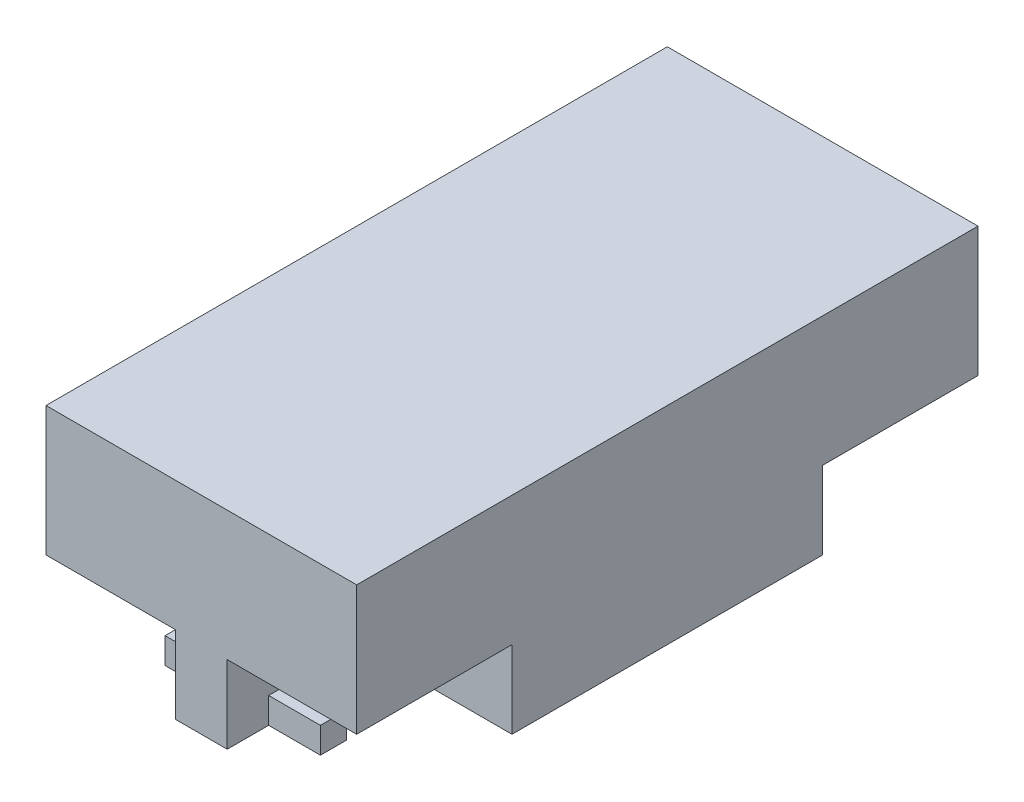
SolidWorks part; units mm, degrees
ref_plane "Front Plane" through (0, 0, 0) normal (0, 0, 1) x (1, 0, 0)
ref_plane "Top Plane" through (0, 0, 0) normal (0, 1, 0) x (1, 0, 0)
ref_plane "Right Plane" through (0, 0, 0) normal (1, 0, 0) x (0, 0, -1)
sketch "Sketch2" plane through (0, 0, 0) normal (1, 0, 0) x (0, 0, -1)
  line L1 (-300, 100) -> (300, 100)
  line L2 (-300, 100) -> (-300, -100)
  line L3 (-300, -100) -> (300, -100)
  line L4 (300, 100) -> (300, -100)
  line L5 (-300, 100) -> (300, -100) construction
  line L6 (-300, -100) -> (300, 100) construction
  point P0 (0, 0)
  dimension "D1" = 600
  dimension "D2" = 200
extrude "Boss-Extrude1" add sketch "Sketch2" along normal blind 150 and the other way blind 150
sketch "Sketch3" plane through (150, 0, 0) normal (1, 0, 0) x (0, 0, -1)
  line L1 (-300, -100) -> (-150, -100)
  line L2 (-300, -100) -> (-300, -25)
  line L3 (-300, -25) -> (-150, -25)
  line L4 (-150, -100) -> (-150, -25)
  line L5 (300, -100) -> (150, -100)
  line L6 (300, -100) -> (300, -25)
  line L7 (300, -25) -> (150, -25)
  line L8 (150, -100) -> (150, -25)
  dimension "D1" = 150
  dimension "D2" = 150
  dimension "D3" = 75
  dimension "D4" = 75
extrude "Cut-Extrude1" cut sketch "Sketch3" against normal blind 125
mirror "Mirror1" about plane through (0, 0, 0) normal (1, 0, 0) of "Cut-Extrude1"
sketch "Sketch4" plane through (25, 0, 0) normal (1, 0, 0) x (0, 0, -1)
  line L0 (-300, -100) -> (-150, -100) construction
  line L1 (-260, -75) -> (-235, -75)
  line L2 (-260, -75) -> (-260, -100)
  line L3 (-260, -100) -> (-235, -100)
  line L4 (-235, -75) -> (-235, -100)
  line L5 (-300, -25) -> (-300, -100) construction
  dimension "D1" = 25
  dimension "D2" = 25
  dimension "D3" = 0
  dimension "D4" = 40
extrude "Boss-Extrude2" add sketch "Sketch4" along normal blind 50
mirror "Mirror2" about plane through (0, 0, 0) normal (1, 0, 0) of "Boss-Extrude2"
mirror "Mirror3" about plane through (0, 0, 0) normal (0, 0, 1) of "Mirror2"
